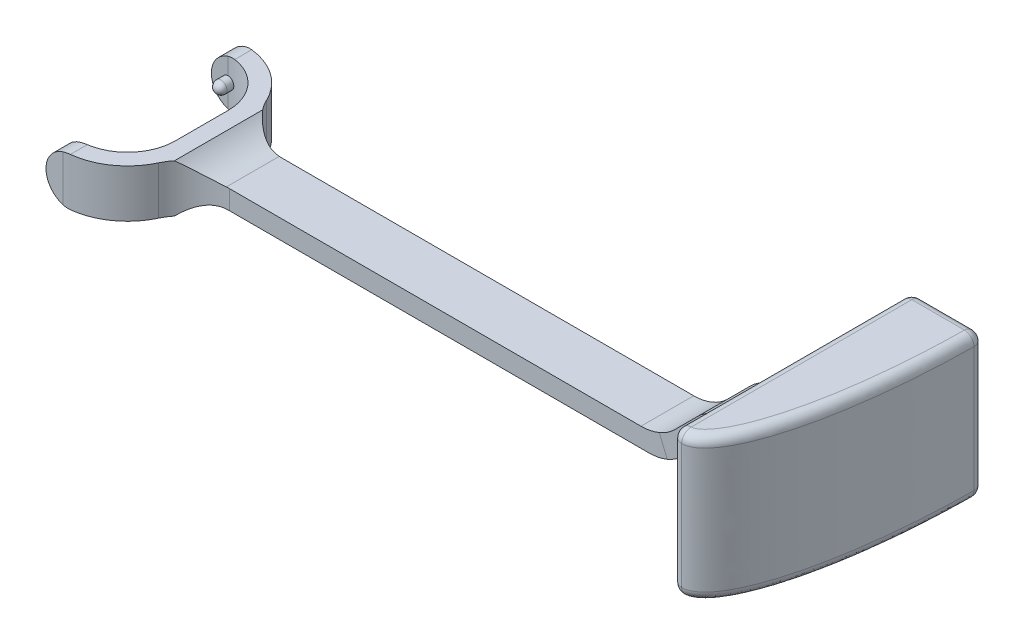
SolidWorks part; units mm, degrees
ref_plane "Front Plane" through (0, 0, 0) normal (0, 0, 1) x (1, 0, 0)
ref_plane "Top Plane" through (0, 0, 0) normal (0, 1, 0) x (1, 0, 0)
ref_plane "Right Plane" through (0, 0, 0) normal (1, 0, 0) x (0, 0, -1)
sketch "Sketch1" plane through (0, 0, 0) normal (1, 0, 0) x (0, 0, -1)
  line L1 (0, 0) -> (11, 0)
  line L2 (0, 0) -> (0, -4)
  line L3 (0, -4) -> (11, -4)
  line L4 (11, 0) -> (11, -4)
  dimension "D1" = 11
  dimension "D2" = 4
extrude "Boss-Extrude1" add sketch "Sketch1" along normal blind 92.5
ref_plane "Plane2" through (0, -3, 0) normal (0, 1, 0) x (1, 0, 0)
sketch3d "3DSketch3"
  line L0 (92.5, -3, -5.5) -> (102.5, -3, -5.5)
  line L1 (102.5, -3, -5.5) -> (113.1066, 7.6066, -5.5)
  line L2 (92.5, 0, -11) -> (92.5, 0, 0) construction
  line L3 (92.5, -4, -11) -> (92.5, 0, -11) construction
  line L4 (113.1066, 7.6066, -5.5) -> (123.1066, 7.6066, -5.5)
  dimension "D1" = 3
  dimension "D2" = 0
  dimension "D3" = 5.5
  dimension "D4" = 135
  dimension "D5" = 10
  dimension "D6" = 15
  dimension "D7" = 10
sketch "Sketch14" plane through (92.5, 0, 0) normal (1, 0, 0) x (0, 0, -1)
  line L1 (0, 0) -> (11, 0)
  line L2 (0, 0) -> (0, -4)
  line L3 (0, -4) -> (11, -4)
  line L4 (11, 0) -> (11, -4)
sweep "Sweep3" add profiles "Sketch14" path "3DSketch3"
fillet "Fillet1" radius 10 4 edges at (102.9142, -4, -5.5) (113.5208, 6.6066, -5.5) (111.864, 10.6066, -5.5) (101.2574, 0, -5.5)
sketch "Sketch16" plane through (123.1066, 0, 0) normal (1, 0, 0) x (0, 0, -1)
  line L1 (30.5, -7.3934) -> (-19.5, -7.3934)
  line L2 (30.5, -7.3934) -> (30.5, 22.6066)
  line L3 (30.5, 22.6066) -> (-19.5, 22.6066)
  line L4 (-19.5, -7.3934) -> (-19.5, 22.6066)
  line L9 (11, 10.6066) -> (0, 10.6066) construction
  line L10 (11, 6.6066) -> (11, 10.6066) construction
  dimension "D1" = 30
  dimension "D2" = 50
  dimension "D3" = 12
  dimension "D4" = 19.5
extrude "Boss-Extrude2" add sketch "Sketch16" along normal blind 15
fillet "Fillet2" radius 13 1 edges at (138.1066, 7.6066, 19.5) second distance 50 first distance on face at (130.6066, 7.6066, 19.5)
fillet "Fillet3" radius 2 13 edges at (123.1066, 8.6066, -11) (123.1066, 6.6066, -5.5) (123.1066, 8.6066, 0) (123.1066, 10.6066, -5.5) (123.1066, 7.6066, 19.5) (123.1066, -7.3934, -5.5) (123.1066, 22.6066, -5.5) (123.1066, 7.6066, -30.5)
sketch "Sketch17" plane through (0, 0, 0) normal (0, 1, 0) x (1, 0, 0)
  line L0 (-10, -10) -> (-13.5, -10)
  line L1 (-13.5, -10) -> (-13.5, -13.5)
  line L2 (-13.5, -13.5) -> (-10, -13.5)
  line L4 (-23.4629, 5.5) -> (20.4079, 5.5) construction
  line L5 (97.1152, 0) -> (0, 0) construction
  line L20 (3.5, 0) -> (3.5, 11)
  line L22 (-13.5, 24.5) -> (-10, 24.5)
  line L23 (0, 0) -> (0, 11)
  line L24 (-13.5, 21) -> (-13.5, 24.5)
  line L25 (-10, 21) -> (-13.5, 21)
  arc A0 (-10, -10) -> (0, 0) centre (-10, 0) ccw
  arc A2 (-10, -13.5) -> (3.5, 0) centre (-10, 0) ccw
  arc A3 (-10, 24.5) -> (3.5, 11) centre (-10, 11) cw
  arc A4 (-10, 21) -> (0, 11) centre (-10, 11) cw
  point P14 (0, 0)
  dimension "D3" = 20
  dimension "D6" = 3.5
  dimension "D1" = 0
  dimension "D2" = 10
  dimension "D5" = 3.5
  dimension "D7" = 5.5
extrude "Boss-Extrude3" add sketch "Sketch17" along normal blind 10 from offset 7 offset against normal yes
fillet "Fillet4" radius 10 2 edges at (3.5, -4, -5.5) (3.5, 0, -5.5)
fillet "Fillet5" radius 10 2 edges at (3.5, -2, 0) (3.5, -2, -11)
fillet "Fillet6" radius 5 4 edges at (-13.5, 3, 11.75) (-13.5, -7, 11.75) (-13.5, -7, -22.75) (-13.5, 3, -22.75)
sketch "Sketch18" plane through (0, 0, -21) normal (0, 0, 1) x (1, 0, 0)
  line L2 (-10, 2.7697) -> (-10, -6.7697) construction
  line L3 (0, 3) -> (-8.5, 3) construction
  circle A0 centre (-10, -2) radius 1.25
  dimension "D1" = 2.5
  dimension "D2" = 0
  dimension "D3" = 5
extrude "Boss-Extrude4" add sketch "Sketch18" along normal blind 1.5
sketch "Sketch19" plane through (0, 0, 10) normal (0, 0, -1) x (-1, 0, 0)
  line L0 (10, 2.7697) -> (10, -6.7697) construction
  circle A0 centre (10, -2) radius 1.25
  dimension "D1" = 2.5
  dimension "D2" = 5
extrude "Boss-Extrude5" add sketch "Sketch19" along normal blind 1.5
ref_plane "CenterOfClips" through (-7.5, 0, 0) normal (-1, 0, 0) x (0, 0, 1)
sketch "Sketch24" plane through (0, 0, 8.5) normal (0, 0, -1) x (-1, 0, 0)
  line L0 (10, -0.75) -> (10, -3.25)
  circle A0 centre (10, -2) radius 1.25 construction
  arc A1 (10, -3.25) -> (10, -0.75) centre (10, -2) ccw
revolve "Revolve9" add sketch "Sketch24" angle 180 about L0
sketch "Sketch25" plane through (0, 0, -19.5) normal (0, 0, 1) x (1, 0, 0)
  line L0 (-10, -0.75) -> (-10, -3.25)
  circle A0 centre (-10, -2) radius 1.25 construction
  arc A1 (-10, -0.75) -> (-10, -3.25) centre (-10, -2) ccw
revolve "Revolve10" add sketch "Sketch25" angle 180 about L0 reverse direction yes
